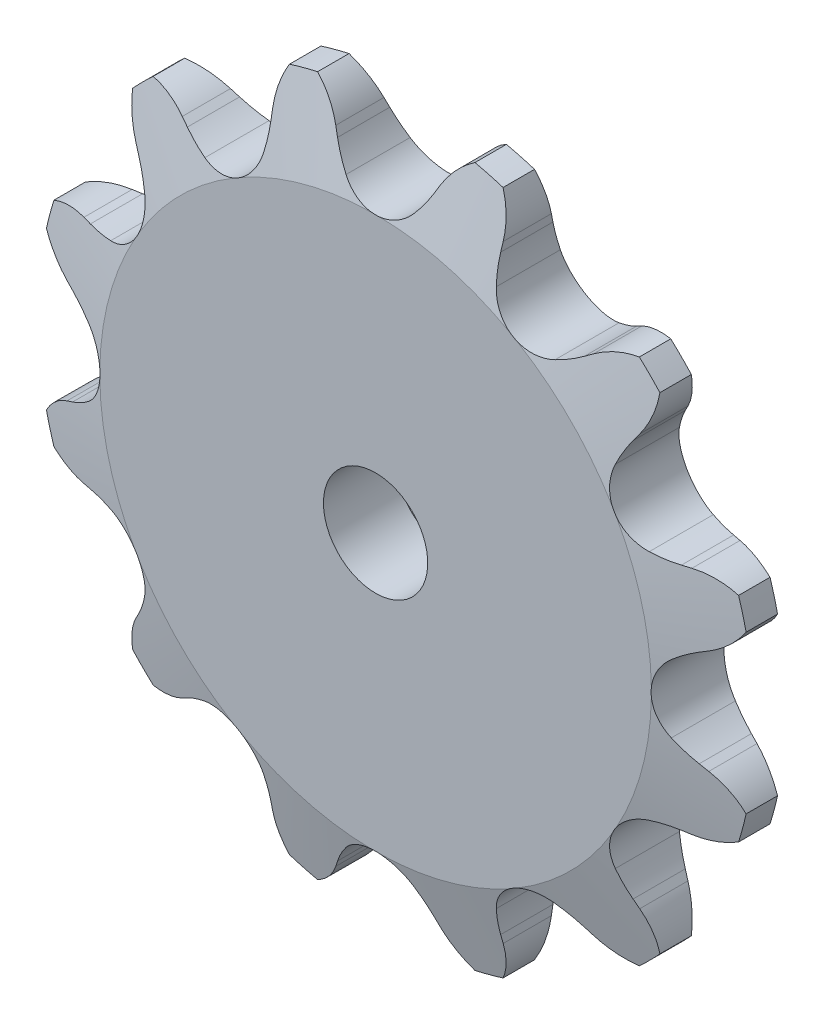
SolidWorks part; units mm, degrees
ref_plane "Front Plane" through (0, 0, 0) normal (0, 0, 1) x (1, 0, 0)
ref_plane "Top Plane" through (0, 0, 0) normal (0, 1, 0) x (1, 0, 0)
ref_plane "Right Plane" through (0, 0, 0) normal (1, 0, 0) x (0, 0, -1)
ref_axis "Axis1" through (0, 0, -88.99) along (0, 0, 1)
sketch "Sprocket-BaseSketch" plane through (0, 0, 0) normal (1, 0, 0) x (0, 0, -1)
  line L0 (1.397, 2) -> (1.397, 10.5793)
  line L1 (1.397, 10.5793) -> (0.6032, 13.7543)
  line L2 (0.6032, 13.7543) -> (-0.6032, 13.7543)
  line L3 (-0.6032, 13.7543) -> (-1.397, 10.5793)
  line L4 (-1.397, 10.5793) -> (-1.397, 2)
  line L5 (-1.397, 2) -> (1.397, 2)
  line L6 (5.588, 0) -> (-1.7463, 0) construction
  dimension "Hub Surface" = 1.397
  dimension "RightSide (1)" = 0.7938
  dimension "RightSide (2)" = 3.175
  dimension "OD" = 13.7543
  dimension "LeftSide (1)" = 0.7938
  dimension "LeftSide (2)" = 3.175
  dimension "Tooth Width" = 2.794
  dimension "Bore" = 2
revolve "25 (04C) ANSI (ISO) Chain Number, 0.966in P.D." add sketch "Sprocket-BaseSketch" angle 360 about L6
sketch "Tooth-Sketch" plane through (0, 0, 0) normal (0, 0, 1) x (1, 0, 0)
  line L0 (0, 0) -> (0, 16.3563) construction
  line L1 (1.8538, 12.0179) -> (2, 12.3089)
  line L2 (-1.8538, 12.0179) -> (-2, 12.3089)
  line L3 (0, 12.2673) -> (6.1336, 10.6238) construction
  line L4 (0, 12.2673) -> (-6.1336, 10.6238) construction
  arc A0 (-1.3002, 11.1762) -> (1.3002, 11.1762) centre (0, 12.2673) ccw
  arc A1 (1.3002, 11.1762) -> (1.8538, 12.0179) centre (-2.0236, 13.9652) ccw
  arc A2 (-1.3002, 11.1762) -> (-1.8538, 12.0179) centre (2.0236, 13.9652) cw
  arc A3 (2, 12.3089) -> (4.4653, 13.8295) centre (4.4653, 11.0708) cw
  arc A4 (-2, 12.3089) -> (-4.4653, 13.8295) centre (-4.4653, 11.0708) ccw
  arc A5 (4.4653, 13.8295) -> (-4.4653, 13.8295) centre (0, 0) ccw
extrude "Tooth-Cut, Number of teeth: 12" cut sketch "Tooth-Sketch" against normal through all and the other way through all
pattern_circular "Tooth Pattern, 12 / 12" count 12 every 30 about axis through (0, 0, -88.99) along (0, 0, 1) of "Tooth-Cut, Number of teeth: 12"
